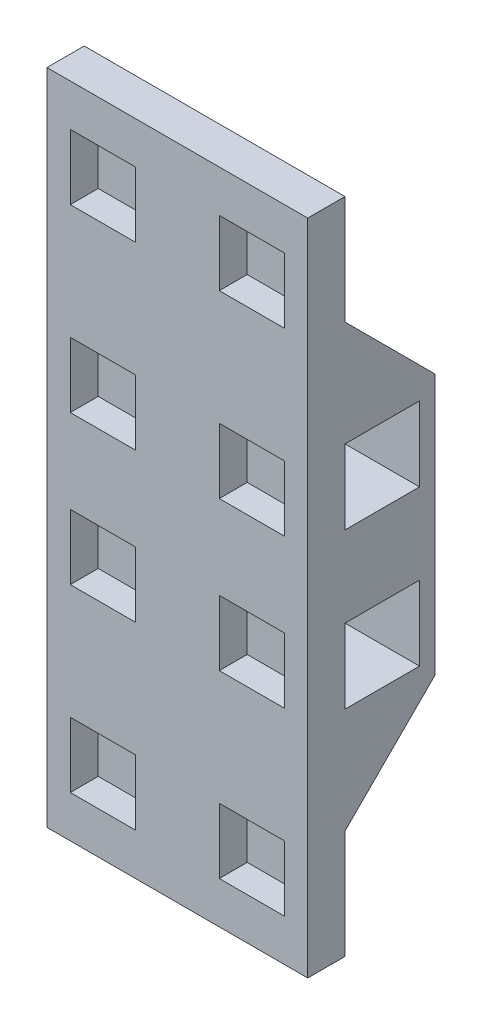
SolidWorks part; units mm, degrees
ref_plane "Plan de face" through (0, 0, 0) normal (0, 0, 1) x (1, 0, 0)
ref_plane "Plan de dessus" through (0, 0, 0) normal (0, 1, 0) x (1, 0, 0)
ref_plane "Plan de droite" through (0, 0, 0) normal (1, 0, 0) x (0, 0, -1)
sketch "Esquisse1" plane through (0, 0, 0) normal (0, 0, 1) x (1, 0, 0)
  line L1 (0, 0) -> (42, 0)
  line L2 (0, 0) -> (0, -42)
  line L3 (0, -42) -> (42, -42)
  line L4 (42, 0) -> (42, -42)
  line L5 (0, -42) -> (42, -42)
  line L6 (42, 0) -> (42, -42)
  line L7 (0, -42) -> (0, -74)
  line L8 (0, 0) -> (42, 0)
  line L9 (0, 0) -> (0, 32)
  line L10 (0, 32) -> (42, 32)
  line L11 (0, -74) -> (42, -74)
  line L12 (42, 0) -> (42, 32)
  line L13 (42, -42) -> (42, -74)
  point P7 (42, -21)
  dimension "D1" = 106
  dimension "D2" = 53
  dimension "D4" = 42
  dimension "D5" = 42
extrude "Boss.-Extru.1" add sketch "Esquisse1" along normal blind 6 contours L4 | L1 L12 L10 L9 | L4 L1 L2 L3 | L13 L3 L7 L11 region at (21, 16, 0) region at (21, -21, 0) region at (21, -58, 0)
sketch "Esquisse2" plane through (0, 0, 0) normal (0, 0, -1) x (-1, 0, 0)
  line L1 (0, -42) -> (-42, -42)
  line L2 (0, -42) -> (0, -25)
  line L3 (0, -25) -> (-42, -25)
  line L4 (-42, -42) -> (-42, -25)
  line L5 (0, 32) -> (0, -74) construction
  line L6 (-42, 32) -> (-42, -74) construction
  line L7 (-42, -74) -> (-42, 32) construction
  point P6 (-42, -21)
  point P7 (-42, -33.5)
  dimension "D1" = 17
  dimension "D2" = 12.5
  dimension "D4" = 0
  dimension "D5" = 0
extrude "Boss.-Extru.3" add sketch "Esquisse2" along normal blind 14.5
sketch "Esquisse3" plane through (42, 0, 0) normal (1, 0, 0) x (0, 0, -1)
  line L1 (12, -39.5) -> (0, -39.5)
  line L2 (12, -39.5) -> (12, -27.5)
  line L3 (12, -27.5) -> (0, -27.5)
  line L4 (0, -39.5) -> (0, -27.5)
  line L5 (14.5, -42) -> (0, -42) construction
  line L6 (0, -74) -> (0, -42) construction
  dimension "D1" = 12
  dimension "D2" = 12
  dimension "D4" = 2.5
extrude "Enlèv. mat.-Extru.3" cut sketch "Esquisse3" against normal through all
ref_plane "Plan1" through (0, -21, 0) normal (0, -1, 0) x (-1, 0, 0)
mirror "Symétrie1" about plane through (0, -21, 0) normal (0, -1, 0) of "Boss.-Extru.3", "Enlèv. mat.-Extru.3"
sketch "Esquisse4" plane through (0, -42, 0) normal (0, -1, 0) x (1, 0, 0)
  line L1 (0, -12) -> (42, -12) construction
  line L2 (42, -14.5) -> (0, -14.5) construction
  circle A0 centre (24.5, -6) radius 2
  circle A1 centre (17.5, -6) radius 2
  point P10 (21, -14.5)
  dimension "D1" = 6
  dimension "D3" = 4
  dimension "D4" = 4
  dimension "D2" = 3.5
  dimension "D5" = 7
  dimension "D6" = 8.5
extrude "Enlèv. mat.-Extru.4" cut sketch "Esquisse4" against normal blind 42
sketch "Esquisse5" plane through (0, 0, 6) normal (0, 0, 1) x (1, 0, 0)
  line L0 (0, 32) -> (42, 32) construction
  line L1 (3.75, -3.75) -> (14.25, -3.75)
  line L2 (3.75, -3.75) -> (3.75, -14.25)
  line L3 (3.75, -14.25) -> (14.25, -14.25)
  line L4 (14.25, -3.75) -> (14.25, -14.25)
  line L5 (-3.3, -21) -> (3.3, -21) construction
  point P4 (14.25, -9)
  point P7 (9, -3.75)
  point P10 (21, 32)
  dimension "D1" = 10.5
  dimension "D2" = 10.5
  dimension "D3" = 12
  dimension "D4" = 12
extrude "Enlèv. mat.-Extru.5" cut sketch "Esquisse5" against normal blind 4.5
ref_plane "Plan2" through (21, 0, 0) normal (1, 0, 0) x (0, 0, -1)
mirror "Symétrie2" about plane through (21, 0, 0) normal (1, 0, 0) of "Enlèv. mat.-Extru.5"
mirror "Symétrie3" about plane through (0, -21, 0) normal (0, -1, 0) of "Symétrie2", "Enlèv. mat.-Extru.5"
ref_plane "Plan3" through (0, -47.5, 0) normal (0, -1, 0) x (-1, 0, 0)
ref_plane "Plan4" through (0, 5.5, 0) normal (0, -1, 0) x (-1, 0, 0)
mirror "Symétrie4" about plane through (0, 5.5, 0) normal (0, -1, 0) of "Symétrie2"
mirror "Symétrie5" about plane through (0, -47.5, 0) normal (0, -1, 0) of face at (3.75, -33, 3.75) of face at (9, -38.25, 3.75) of face at (33, -38.25, 3.75) of face at (27.75, -33, 3.75) of face at (33, -27.75, 3.75) of face at (38.25, -33, 3.75) of face at (14.25, -33, 3.75) of face at (9, -27.75, 3.75) of face at (9, -33, 1.5) of face at (33, -33, 1.5)
sketch "Esquisse6" plane through (0, 0, 0) normal (-1, 0, 0) x (0, 0, 1)
  line L0 (-14.5, -42) -> (0, -56.5)
  line L1 (0, -74) -> (0, -42) construction
  line L2 (0, -56.5) -> (0, -42)
  line L3 (0, -42) -> (-14.5, -42)
  dimension "D1" = 45
extrude "Boss.-Extru.4" add sketch "Esquisse6" against normal blind 4
sketch "Esquisse7" plane through (0, 0, 0) normal (0, 0, -1) x (-1, 0, 0)
  line L0 (-4, -56.5) -> (-12.3716, -42)
  line L1 (-42, -42) -> (-4, -42) construction
  line L2 (-12.3716, -42) -> (-4, -42)
  line L3 (-4, -42) -> (-4, -56.5)
  dimension "D1" = 60
extrude "Boss.-Extru.5" add sketch "Esquisse7" along normal up to surface (14.5 mm away) up to face at (2, -49.25, -7.25)
ref_axis "Axe1" through (21, -21, 7.025) along (0, 0, -1)
pattern_circular "Répétition circulaire1" count 2 every 180 about axis through (21, -21, 7.025) along (0, 0, -1) of "Boss.-Extru.5", "Boss.-Extru.4"
mirror "Symétrie6" about plane through (21, 0, 0) normal (1, 0, 0) of "Répétition circulaire1"
sketch "Esquisse8" plane through (0, 0, 0) normal (0, 0, -1) x (-1, 0, 0)
  line L0 (0, -25) -> (-42, -25) construction
  line L1 (0, -17) -> (-12, -17)
  line L2 (0, -17) -> (0, -25)
  line L3 (0, -25) -> (-12, -25)
  line L4 (-12, -17) -> (-12, -25)
  dimension "D1" = 12
extrude "Boss.-Extru.6" add sketch "Esquisse8" along normal up to surface (14.5 mm away) up to face at (21, -5.6667, -14.5)
chamfer "Chanfrein2" distance 15 angle 30 1 edges at (12, -21, -14.5) first distance on face at (12, -21, -7.25)
mirror "Symétrie7" about plane through (21, 0, 0) normal (1, 0, 0) of "Chanfrein2", "Boss.-Extru.6"
equation "\"é\"=1.5583"
equation "\"à\"=2.55842"
